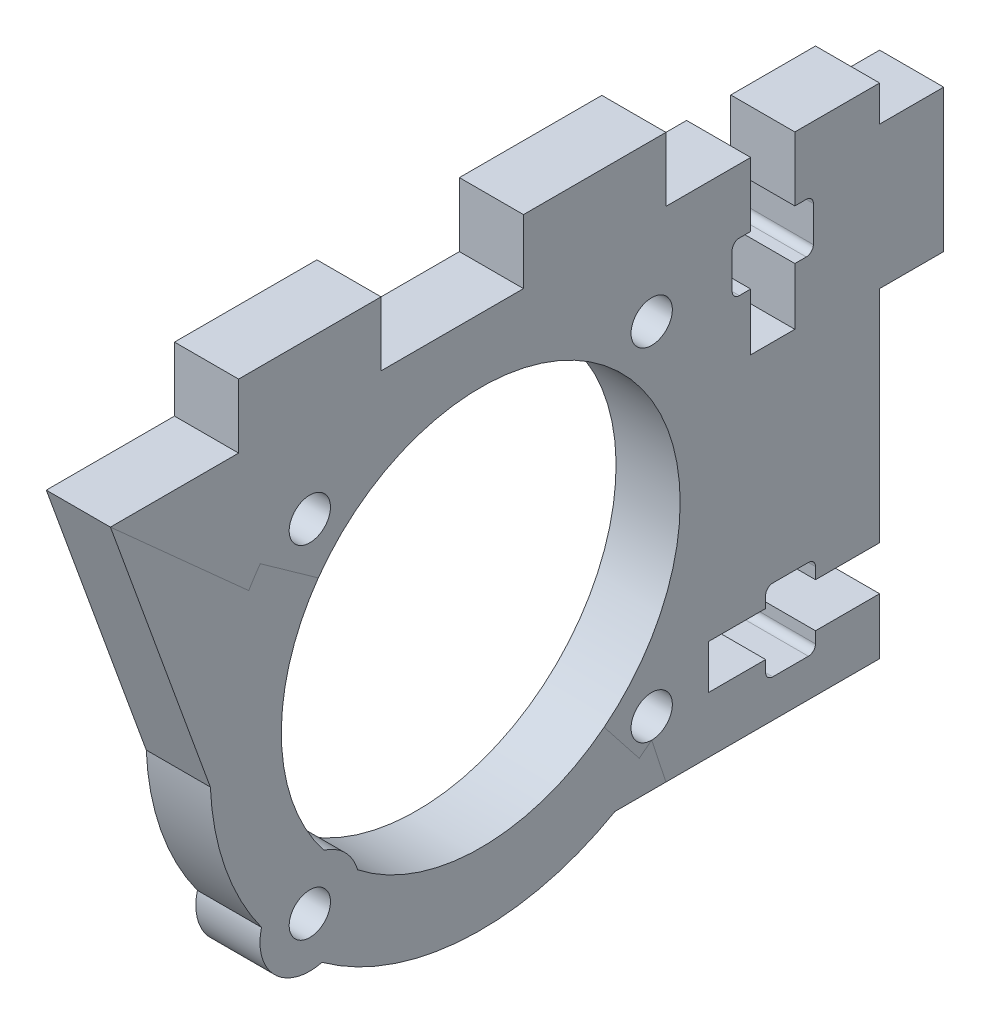
SolidWorks part; units mm, degrees
ref_plane "Front Plane" through (0, 0, 0) normal (0, 0, 1) x (1, 0, 0)
ref_plane "Top Plane" through (0, 0, 0) normal (0, 1, 0) x (1, 0, 0)
ref_plane "Right Plane" through (0, 0, 0) normal (1, 0, 0) x (0, 0, -1)
sketch "Sketch1" plane through (0, 0, 0) normal (1, 0, 0) x (0, 0, -1)
  line L0 (0, 0) -> (0, -35)
  line L1 (0, -35) -> (-54, 0)
  line L2 (-54, 0) -> (0, 0)
  dimension "D1" = 35
  dimension "D2" = 54
extrude "Boss-Extrude1" add sketch "Sketch1" along normal blind 4.5
sketch "Sketch2" plane through (4.5, 0, 0) normal (1, 0, 0) x (0, 0, -1)
  line L0 (0, -35) -> (0, 0) construction
  line L1 (-4.5, -2.5) -> (4.5, -2.5)
  line L2 (-4.5, -2.5) -> (-4.5, -12.5)
  line L3 (-4.5, -12.5) -> (4.5, -12.5)
  line L4 (4.5, -2.5) -> (4.5, -12.5)
  line L5 (-4.5, -2.5) -> (4.5, -12.5) construction
  line L6 (-4.5, -12.5) -> (4.5, -2.5) construction
  line L7 (0, 0) -> (-54, 0) construction
  point P0 (0, -7.5)
  dimension "D1" = 10
  dimension "D2" = 7.5
  dimension "D3" = 4.5
extrude "Boss-Extrude2" add sketch "Sketch2" against normal through all
sketch "Sketch3" plane through (4.5, 0, 0) normal (1, 0, 0) x (0, 0, -1)
  line L0 (0, -35) -> (-15, -35)
  line L1 (0, -25) -> (-54, 0)
  line L4 (0, -35) -> (0, -12.5) construction
  line L5 (0, -25) -> (0, -35)
  line L6 (-54, 0) -> (-15, -35)
  dimension "D1" = 15
  dimension "D2" = 10
extrude "Boss-Extrude3" add sketch "Sketch3" against normal through all
sketch "Sketch4" plane through (4.5, 0, 0) normal (1, 0, 0) x (0, 0, -1)
  line L0 (0, -29.5) -> (-12, -29.5) construction
  line L1 (0, -35) -> (0, -12.5) construction
  line L2 (0, -27.95) -> (-12, -27.95) construction
  line L3 (-12, -27.95) -> (-12, -31.05) construction
  line L4 (0, -31.05) -> (0, -27.95)
  line L5 (0, -27.95) -> (-4.5, -27.95)
  line L6 (-4.5, -27.95) -> (-4.5, -27.15)
  line L7 (-5, -26.65) -> (-7.5, -26.65)
  line L8 (-8, -27.15) -> (-8, -27.95)
  line L9 (-8, -27.95) -> (-12, -27.95)
  line L10 (-12, -27.95) -> (-12, -31.05)
  line L12 (0, -31.05) -> (-12, -31.05) construction
  line L13 (-8, -31.05) -> (-12, -31.05)
  line L14 (-8, -31.85) -> (-8, -31.05)
  line L15 (-5, -32.35) -> (-7.5, -32.35)
  line L16 (-4.5, -31.05) -> (-4.5, -31.85)
  line L17 (0, -31.05) -> (-4.5, -31.05)
  line L18 (4.5, -12.5) -> (4.5, -2.5) construction
  line L19 (0, -18.5) -> (-33.3857, -18.5) construction
  line L20 (-54, 0) -> (-15, -35) construction
  line L37 (0, -31.05) -> (-12, -31.05) construction
  arc A0 (-8, -31.85) -> (-7.5, -32.35) centre (-7.5, -31.85) ccw
  arc A1 (-5, -32.35) -> (-4.5, -31.85) centre (-5, -31.85) ccw
  arc A2 (-4.5, -27.15) -> (-5, -26.65) centre (-5, -27.15) ccw
  arc A3 (-7.5, -26.65) -> (-8, -27.15) centre (-7.5, -27.15) ccw
  point P10 (4.5, -7.5)
  point P20 (-8, -32.35)
  point P23 (-4.5, -32.35)
  point P26 (-4.5, -26.65)
  point P29 (-8, -26.65)
  dimension "D7" = 0.5
  dimension "D1" = 12
  dimension "D2" = 1.55
  dimension "D3" = 2.85
  dimension "D4" = 3.5
  dimension "D5" = 8
  dimension "D6" = 22
extrude "Cut-Extrude1" cut sketch "Sketch4" against normal through all
sketch "Sketch5" plane through (4.5, 0, 0) normal (1, 0, 0) x (0, 0, -1)
  line L0 (0, 0) -> (-54, 0) construction
  line L1 (-25, 4.5) -> (-15, 4.5)
  line L2 (-25, 4.5) -> (-25, 0)
  line L3 (0, 0) -> (-54, 0) construction
  line L4 (-15, 4.5) -> (-15, 0)
  line L5 (-25, 4.5) -> (-20, 0) construction
  line L6 (-20, 0) -> (-15, 4.5) construction
  line L7 (-30, 0) -> (-30, 4.5) construction
  line L8 (-40, 0) -> (-45, 4.5) construction
  line L9 (-35, 4.5) -> (-40, 0) construction
  line L10 (-45, 4.5) -> (-45, 0)
  line L12 (-35, 4.5) -> (-35, 0)
  line L13 (-35, 4.5) -> (-45, 4.5)
  line L14 (-20, 0) -> (-15, 4.5) construction
  line L15 (-15, 0) -> (-25, 0)
  line L16 (-35, 0) -> (-45, 0)
  point P0 (-20, 0)
  point P14 (-40, 0)
  dimension "D3" = 4.5
  dimension "D1" = 20
  dimension "D2" = 10
  dimension "D4" = 20
  dimension "D5" = 5
extrude "Boss-Extrude4" add sketch "Sketch5" against normal through all
sketch "Sketch8" [suppressed] plane through (4.5, 0, 0) normal (1, 0, 0) x (0, 0, -1)
  line L0 (-15, -30) -> (-27, -30) construction
  line L1 (-15, -35) -> (-27, -35)
  line L2 (-15, -25) -> (-27, -25)
  line L3 (-15, -35) -> (0, -35) construction
  line L4 (-15, -25) -> (-15, -35)
  arc A1 (-27, -25) -> (-27, -35) centre (-27, -30) ccw
  dimension "D5" = 5
  dimension "D1" = 0
  dimension "D2" = 12
  dimension "D3" = 0
  dimension "D4" = 10
extrude "Boss-Extrude5" [suppressed] add sketch "Sketch8" against normal up to surface (4.5 mm away) up to face at (0, -17.3125, 11.9375)
sketch "Sketch9" [suppressed] plane through (4.5, 0, 0) normal (1, 0, 0) x (0, 0, -1)
  line L0 (-27, -30) -> (-22, -30) construction
  line L1 (-27, -27) -> (-22, -27)
  line L2 (-27, -33) -> (-22, -33)
  arc A0 (-27, -27) -> (-27, -33) centre (-27, -30) ccw
  arc A1 (-22, -33) -> (-22, -27) centre (-22, -30) ccw
  point P3 (-24.5, -30)
  dimension "D1" = 3
  dimension "D2" = 5
extrude "Cut-Extrude3" [suppressed] cut sketch "Sketch9" against normal through all
sketch "Sketch10" plane through (0, 0, 0) normal (-1, 0, 0) x (0, 0, 1)
  line L0 (15, -35) -> (54, -12)
  line L1 (54, -12) -> (54, 0)
  line L3 (54, 0) -> (15, -35)
  dimension "D1" = 12
extrude "Boss-Extrude6" [suppressed] add sketch "Sketch10" against normal through all
sketch "Sketch6" plane through (4.5, 0, 0) normal (1, 0, 0) x (0, 0, -1)
  line L0 (-30, 0) -> (-30, -11) construction
  line L1 (-25, 0) -> (-35, 0) construction
  line L2 (-28.45, -11) -> (-31.55, -11) construction
  line L3 (-31.55, -11) -> (-31.55, 0) construction
  line L4 (-28.45, 0) -> (-31.55, 0)
  line L5 (-31.55, 0) -> (-31.55, -4.5)
  line L6 (-31.55, -4.5) -> (-32.35, -4.5)
  line L7 (-32.85, -5) -> (-32.85, -7.5)
  line L8 (-32.35, -8) -> (-31.55, -8)
  line L9 (-31.55, -8) -> (-31.55, -11)
  line L10 (-31.55, -11) -> (-28.45, -11)
  line L11 (-28.45, -11) -> (-28.45, 0) construction
  line L12 (-28.45, -8) -> (-28.45, -11)
  line L13 (-27.65, -8) -> (-28.45, -8)
  line L14 (-27.15, -5) -> (-27.15, -7.5)
  line L15 (-28.45, -4.5) -> (-27.65, -4.5)
  line L16 (-28.45, 0) -> (-28.45, -4.5)
  arc A0 (-32.85, -7.5) -> (-32.35, -8) centre (-32.35, -7.5) ccw
  arc A1 (-32.35, -4.5) -> (-32.85, -5) centre (-32.35, -5) ccw
  arc A2 (-27.65, -4.5) -> (-27.15, -5) centre (-27.65, -5) cw
  arc A3 (-27.15, -7.5) -> (-27.65, -8) centre (-27.65, -7.5) cw
  point P12 (-32.85, -8)
  point P15 (-32.85, -4.5)
  point P26 (-27.15, -4.5)
  point P27 (-27.15, -8)
  dimension "D2" = 1.55
  dimension "D4" = 3.5
  dimension "D6" = 0.5
  dimension "D1" = 11
  dimension "D3" = 8
  dimension "D5" = 2.85
extrude "Cut-Extrude2" [suppressed] cut sketch "Sketch6" against normal through all
sketch "Sketch11" plane through (0, 0, 0) normal (-1, 0, 0) x (0, 0, 1)
  line L0 (7.5, 0) -> (7.5, -12) construction
  line L1 (0, 0) -> (15, 0) construction
  line L2 (5.95, -12) -> (9.05, -12)
  line L3 (9.05, -12) -> (9.05, -8)
  line L4 (9.05, -8) -> (9.85, -8)
  line L5 (10.35, -7.5) -> (10.35, -5)
  line L6 (9.85, -4.5) -> (9.05, -4.5)
  line L7 (9.05, -4.5) -> (9.05, 0)
  line L8 (9.05, 0) -> (5.95, 0)
  line L9 (9.05, -8) -> (9.05, -4.5) construction
  line L10 (0, 0) -> (15, 0) construction
  line L11 (5.95, -8) -> (5.95, -4.5) construction
  line L12 (5.95, -4.5) -> (5.95, 0)
  line L13 (5.15, -4.5) -> (5.95, -4.5)
  line L14 (4.65, -7.5) -> (4.65, -5)
  line L15 (5.95, -8) -> (5.15, -8)
  line L16 (5.95, -12) -> (5.95, -8)
  arc A0 (10.35, -5) -> (9.85, -4.5) centre (9.85, -5) ccw
  arc A1 (5.15, -4.5) -> (4.65, -5) centre (5.15, -5) ccw
  arc A2 (9.85, -8) -> (10.35, -7.5) centre (9.85, -7.5) ccw
  arc A3 (4.65, -7.5) -> (5.15, -8) centre (5.15, -7.5) ccw
  point P11 (7.5, 0)
  point P22 (10.35, -4.5)
  point P25 (4.65, -4.5)
  point P28 (10.35, -8)
  point P31 (4.65, -8)
  dimension "D7" = 0.5
  dimension "D1" = 12
  dimension "D3" = 2.85
  dimension "D8" = 0.5
  dimension "D2" = 3.5
  dimension "D4" = 8
  dimension "D5" = 1.55
  dimension "D6" = 0
extrude "Cut-Extrude4" cut sketch "Sketch11" against normal through all
sketch "Sketch12" plane through (0, 0, 0) normal (-1, 0, 0) x (0, 0, 1)
  line L0 (28, -18.5) -> (16, -6.5) construction
  line L1 (28, -18.5) -> (28, -4.5) construction
  line L2 (28, -18.5) -> (40, -6.5) construction
  line L3 (28, -18.5) -> (14, -18.5) construction
  line L4 (28, -18.5) -> (16, -30.5) construction
  line L5 (28, -18.5) -> (16, -6.5) construction
  line L6 (0, -27.95) -> (0, -12.5) construction
  line L7 (25, 0) -> (35, 0) construction
  circle A0 centre (28, -18.5) radius 14
  circle A1 centre (16, -6.5) radius 1.45
  circle A2 centre (40, -6.5) radius 1.45
  circle A3 centre (16, -30.5) radius 1.45
  dimension "D1" = 28
  dimension "D2" = 2.9
  dimension "D3" = 12
  dimension "D4" = 45
  dimension "D5" = 28
  dimension "D6" = 18.5
extrude "FanCutout" cut sketch "Sketch12" against normal through all
sketch "Sketch13" plane through (0, 0, 0) normal (-1, 0, 0) x (0, 0, 1)
  line L0 (39.4071, -10.3834) -> (43.481, -7.4847)
  line L1 (19.3358, -29.4969) -> (16.2414, -33.4243)
  line L6 (28, -18.5) -> (54, 0) construction
  line L7 (28, -18.5) -> (15, -35) construction
  arc A0 (19.3358, -29.4969) -> (39.4071, -10.3834) centre (28, -18.5) ccw
  arc A1 (16.2414, -33.4243) -> (43.481, -7.4847) centre (28, -18.5) ccw
  arc A3 (40.4722, -12.1404) -> (20.333, -30.214) centre (28, -18.5) ccw construction
  dimension "D1" = 5
extrude "Boss-Extrude7" add sketch "Sketch13" against normal through all
sketch "Sketch14" plane through (0, 0, 0) normal (-1, 0, 0) x (0, 0, 1)
  line L0 (28, -4.5) -> (28, -32.5) construction
  line L1 (28, -18.5) -> (40, -30.5) construction
  circle A0 centre (28, -18.5) radius 14 construction
  circle A1 centre (40, -30.5) radius 3.5
  dimension "D2" = 7
  dimension "D1" = 45
  dimension "D3" = 12
extrude "Boss-Extrude8" add sketch "Sketch14" against normal through all
sketch "Sketch15" plane through (0, 0, 0) normal (-1, 0, 0) x (0, 0, 1)
  line L0 (42.4749, -32.9749) -> (28, -18.5) construction
  arc A0 (39.1388, -33.8924) -> (43.3924, -29.6388) centre (40, -30.5) ccw construction
  circle A1 centre (40, -30.5) radius 1.45
  dimension "D1" = 2.9
extrude "Cut-Extrude6" cut sketch "Sketch15" against normal through all
sketch "Sketch16" [suppressed] plane through (4.5, 0, 0) normal (1, 0, 0) x (0, 0, -1)
  line L0 (0, -34.5) -> (-39, -34.5) construction
  line L1 (0, -27.95) -> (0, -12.5) construction
  line L2 (-15, -34.5) -> (-39, -34.5) construction
  line L3 (-15, -38.5) -> (-39, -38.5)
  line L4 (-15, -30.5) -> (-39, -30.5)
  arc A0 (-15, -38.5) -> (-15, -30.5) centre (-15, -34.5) ccw
  arc A1 (-39, -30.5) -> (-39, -38.5) centre (-39, -34.5) ccw
  point P5 (-27, -34.5)
  point P12 (0, -20.225)
  dimension "D1" = 4
  dimension "D2" = 34.5
  dimension "D3" = 39
  dimension "D4" = 15
extrude "Boss-Extrude9" [suppressed] add sketch "Sketch16" against normal through all
sketch "Sketch17" [suppressed] plane through (4.5, 0, 0) normal (1, 0, 0) x (0, 0, -1)
  line L0 (-43, -34.5) -> (0, -34.5) construction
  line L1 (0, -27.75) -> (0, -12.5) construction
  line L2 (-26.5, -34.5) -> (-26.5, -20.0064) construction
  arc A0 (-42.1823, -32.0766) -> (-39, -38.5) centre (-39, -34.5) ccw construction
  circle A1 centre (-39, -34.5) radius 1.55
  circle A2 centre (-14, -34.5) radius 1.55
  dimension "D1" = 2.9
  dimension "D2" = 12.5
extrude "Cut-Extrude7" [suppressed] cut sketch "Sketch17" against normal through all
sketch "Sketch18" [suppressed] plane through (4.5, 0, 0) normal (1, 0, 0) x (0, 0, -1)
  line L0 (-15, -38.5) -> (0, -35)
  line L1 (0, -35) -> (-11.0314, -35)
  line L2 (-11.0314, -35) -> (-15, -38.5)
extrude "Boss-Extrude10" [suppressed] add sketch "Sketch18" against normal through all
sketch "Sketch20" [suppressed] plane through (4.5, 0, 0) normal (1, 0, 0) x (0, 0, -1)
  line L0 (0, -35) -> (0, -31.05) construction
  line L1 (-9, -38) -> (-37.9081, -38)
  line L2 (-40.7232, -36.0371) -> (-54, 0)
  line L3 (-54, 0) -> (-15, -35)
  line L4 (-15, -35) -> (-6, -35)
  line L5 (-9, -38) -> (-6, -35)
  line L6 (-40.7232, -36.0371) -> (-40, -38) construction
  line L7 (-40, -38) -> (-37.9081, -38) construction
  arc A1 (-37.9081, -38) -> (-40.7232, -36.0371) centre (-37.9081, -35) cw
  point P0 (0, -33.025)
  point P14 (-40, -38)
  dimension "D3" = 6
  dimension "D4" = 3
  dimension "D1" = 40
  dimension "D2" = 3
  dimension "D5" = 135
extrude "Boss-Extrude11" [suppressed] add sketch "Sketch20" against normal through all
sketch "Sketch21" [suppressed] plane through (4.5, 0, 0) normal (1, 0, 0) x (0, 0, -1)
  line L0 (0, -34.5) -> (-41.2895, -34.5) construction
  line L1 (0, -35) -> (0, -31.05) construction
  line L2 (-54, 0) -> (-40.7232, -36.0371) construction
  line L3 (0, -27.95) -> (0, -12.5) construction
  circle A0 centre (-36, -34.5) radius 1.45
  circle A1 centre (-11, -34.5) radius 1.45
  dimension "D2" = 2.9
  dimension "D3" = 2.9
  dimension "D1" = 25
  dimension "D4" = 34.5
  dimension "D5" = 11
extrude "Cut-Extrude8" [suppressed] cut sketch "Sketch21" against normal through all
sketch "Sketch22" [suppressed] plane through (4.5, 0, 0) normal (1, 0, 0) x (0, 0, -1)
  line L0 (0, -27.95) -> (0, -12.5) construction
  line L1 (-25, 0) -> (-35, 0) construction
  circle A0 centre (-28, -18) radius 13.25
  dimension "D2" = 18
  dimension "D3" = 26.5
  dimension "D1" = 28
extrude "Cut-Extrude9" [suppressed] cut sketch "Sketch22" against normal through all
sketch "Sketch24" plane through (0, 0, 0) normal (-1, 0, 0) x (0, 0, 1)
  line L0 (15, -35) -> (20, -35)
  line L1 (20, -35) -> (16, -31.95)
  line L2 (16, -31.95) -> (15, -35)
  circle A0 centre (16, -30.5) radius 1.45 construction
  dimension "D1" = 5
extrude "Boss-Extrude13" add sketch "Sketch24" against normal through all
sketch "Sketch25" plane through (0, 0, 0) normal (-1, 0, 0) x (0, 0, 1)
  line L0 (54, 0) -> (46.9826, -19.3121)
  line L1 (46.9826, -19.3121) -> (44.2874, -8.7164)
  line L2 (44.2874, -8.7164) -> (54, 0)
  arc A0 (43.3924, -29.6388) -> (44.2874, -8.7164) centre (28, -18.5) ccw construction
extrude "Boss-Extrude15" add sketch "Sketch25" against normal through all
equation "\"X-ROD-SPACING\"=45"
equation "\"Y-ROD-SPACING\"=75"
equation "\"Z-ROD-SPACING\"=17.5"
equation "\"Y-BED-OFFSET\"=2"
equation "\"Y-BED-ROD-INSET\"=3.5"
equation "\"Y-BED-SCREW-SPACING\"=209"
equation "\"Y-BED-SCREW-CUTOUT-SLOT-HEIGHT\"=2"
equation "\"T-SLOT-NUT-FILLET-RADIUS\"=0.5"
equation "\"T-SLOT-SCREW-SHAFT-RADIUS\"=1.55"
equation "\"T-SLOT-SCREW-SHAFT-CUTOUT-LENGTH\"=11"
equation "\"T-SLOT-NUT-DEPTH\"=3.5"
equation "\"T-SLOT-NUT-WIDTH\"=2.85"
equation "\"T-SLOT-NUT-END-DISTANCE\"=8"
equation "\"ACRYLIC-THICKNESS\"=10"
equation "\"ACRYLIC-THICKNESS2\"=4.5"
equation "\"ACRYLIC-TAB-CUTOUT-SIZE\"=\"ACRYLIC-THICKNESS\"+\"ACRYLIC-TAB-TOLERANCE\"*2"
equation "\"ACRYLIC-TAB-WIDTH\"=\"ACRYLIC-THICKNESS\""
equation "\"ACRYLIC-M3-HOLE\"=2.9"
equation "\"SMOOTHROD-CAP-SCREW-DISTANCE\"=20"
equation "\"FRAME-WIDTH-INNER\"=370"
equation "\"NEMA17-HOLE-SPACING\"=31"
equation "\"NEMA17-CENTRAL-CUTOUT\"=22.5"
equation "\"Z-BRACKET-REACH\"=55"
equation "\"Z-ROD-INSET\"=13.5"
equation "\"TOP-BRACKET-SPACING\"=40"
equation "\"SMOOTHROD-X-LENGTH\"=350"
equation "\"SMOOTHROD-Y-LENGTH\"=350"
equation "\"SMOOTHROD-Z-LENGTH\"=350"
equation "\"SMOOTHROD-TIGHTENING-HEADROOM\"=.25"
equation "\"LEADSCREW-Z-LENGTH\"=300"
equation "\"SCREW-LENGTH-FRAME\"=\"ACRYLIC-THICKNESS\" + 10"
equation "\"SCREW-LENGTH-MOTOR\"=\"ACRYLIC-THICKNESS\" + 5"
equation "\"SCREW-LENGTH-EXTRUDER\"=28"
equation "\"SCREW-HEAD-RADIUS\"=6"
equation "\"PRINTED-X-SMOOTHROD-DIAMETER\"=8.8"
equation "\"PRINTED-X-SMOOTHROD-CUTOUT\"=10"
equation "\"PRINTED-X-BASE-HEIGHT\"=10"
equation "\"PRINTED-LM8UU-CUTOUT-SIZE\"=15.5"
equation "\"PRINTED-LM8UU-CUTOUT-LENGTH\"=24.5"
equation "\"PRINTED-X-IDLER-HEIGHT\"=16"
equation "\"PSU-MOUNTING-WIDTH\"=95"
equation "\"PSU-MOUNTING-HEIGHT\"=177"
equation "\"Y-BELT-TO-ROD-DISTANCE\"=20"
equation "\"SPOOL-HOLDER-ROD-SPACING\"=150"
equation "\"ACRYLIC-X-CARRIAGE-WIDTH\"=55"
equation "\"ACRYLIC-X-CARRIAGE-HEIGHT\"=75"
equation "\"ACRYLIC-X-CARRIAGE-SCREW-SPACING-X\"=15"
equation "\"ACRYLIC-X-CARRIAGE-SCREW-SPACING-Y\"=33"
equation "\"ACRYLIC-X-CARRIAGE-CENTER-TAB-SPACING\"=14"
equation "\"ACRYLIC-X-CARRIAGE-EXTRUDER-SHELF-DEPTH\"=\"ACRYLIC-X-CARRIAGE-EXTRUDER-OFFSET\" + 28"
equation "\"D2@Sketch1\"=\"ACRYLIC-X-CARRIAGE-EXTRUDER-SHELF-DEPTH\""
equation "\"D1@Boss-Extrude1\"=\"ACRYLIC-THICKNESS2\""
equation "\"D1@Sketch2\"=\"ACRYLIC-TAB-WIDTH\""
equation "\"D3@Sketch2\"=\"ACRYLIC-THICKNESS2\""
equation "\"ACRYLIC-X-CARRIAGE-LM8UU-CUTOUT-WIDTH\"=24.25"
equation "\"ACRYLIC-X-CARRIAGE-EXTRUDER-BRACE-SPACING\"=23"
equation "\"ACRYLIC-X-CARRIAGE-EXTRUDER-BRACE-HEIGHT\"=35"
equation "\"D1@Sketch1\"=\"ACRYLIC-X-CARRIAGE-EXTRUDER-BRACE-HEIGHT\""
equation "\"D1@Sketch4\"=\"T-SLOT-SCREW-SHAFT-CUTOUT-LENGTH\"+1"
equation "\"D2@Sketch4\"=\"T-SLOT-SCREW-SHAFT-RADIUS\""
equation "\"D3@Sketch4\"=\"T-SLOT-NUT-WIDTH\""
equation "\"D4@Sketch4\"=\"T-SLOT-NUT-DEPTH\""
equation "\"D5@Sketch4\"=\"T-SLOT-NUT-END-DISTANCE\""
equation "\"D7@Sketch4\"=\"T-SLOT-NUT-FILLET-RADIUS\""
equation "\"ACRYLIC-X-CARRIAGE-EXTRUDER-BRACE-SCREW-SPACING\"=22"
equation "\"D6@Sketch4\"=\"ACRYLIC-X-CARRIAGE-EXTRUDER-BRACE-SCREW-SPACING\""
equation "\"ACRYLIC-X-CARRIAGE-EXTRUDER-BRACE-TAB-OFFSET\"=20"
equation "\"D1@Sketch5\"=\"ACRYLIC-X-CARRIAGE-EXTRUDER-BRACE-TAB-OFFSET\""
equation "\"D2@Sketch5\"=\"ACRYLIC-TAB-WIDTH\""
equation "\"D3@Sketch5\"=\"ACRYLIC-THICKNESS2\""
equation "\"ACRYLIC-X-CARRIAGE-EXTRUDER-OFFSET\"=26"
equation "\"ACRYLIC-X-CARRIAGE-EXTRUDER-ANGLE\"=90"
equation "\"D1@Sketch6\"=\"T-SLOT-SCREW-SHAFT-CUTOUT-LENGTH\""
equation "\"D2@Sketch6\"=\"T-SLOT-SCREW-SHAFT-RADIUS\""
equation "\"D3@Sketch6\"=\"T-SLOT-NUT-END-DISTANCE\""
equation "\"D4@Sketch6\"=\"T-SLOT-NUT-DEPTH\""
equation "\"D5@Sketch6\"=\"T-SLOT-NUT-WIDTH\""
equation "\"D6@Sketch6\"=\"T-SLOT-NUT-FILLET-RADIUS\""
equation "\"D1@Sketch11\"=\"T-SLOT-SCREW-SHAFT-CUTOUT-LENGTH\"+1"
equation "\"D2@Sketch11\"=\"T-SLOT-NUT-DEPTH\""
equation "\"D3@Sketch11\"=\"T-SLOT-NUT-WIDTH\""
equation "\"D4@Sketch11\"=\"T-SLOT-NUT-END-DISTANCE\""
equation "\"D5@Sketch11\"=\"T-SLOT-SCREW-SHAFT-RADIUS\""
equation "\"D7@Sketch11\"=\"T-SLOT-NUT-FILLET-RADIUS\""
equation "\"D8@Sketch11\"=\"T-SLOT-NUT-FILLET-RADIUS\""
equation "\"D2@Sketch12\"=\"ACRYLIC-M3-HOLE\""
equation "\"D1@Sketch15\"=\"ACRYLIC-M3-HOLE\""
equation "\"D1@Sketch17\"=\"ACRYLIC-M3-HOLE\""
equation "\"D2@Sketch21\"=\"ACRYLIC-M3-HOLE\""
equation "\"D3@Sketch21\"=\"ACRYLIC-M3-HOLE\""
